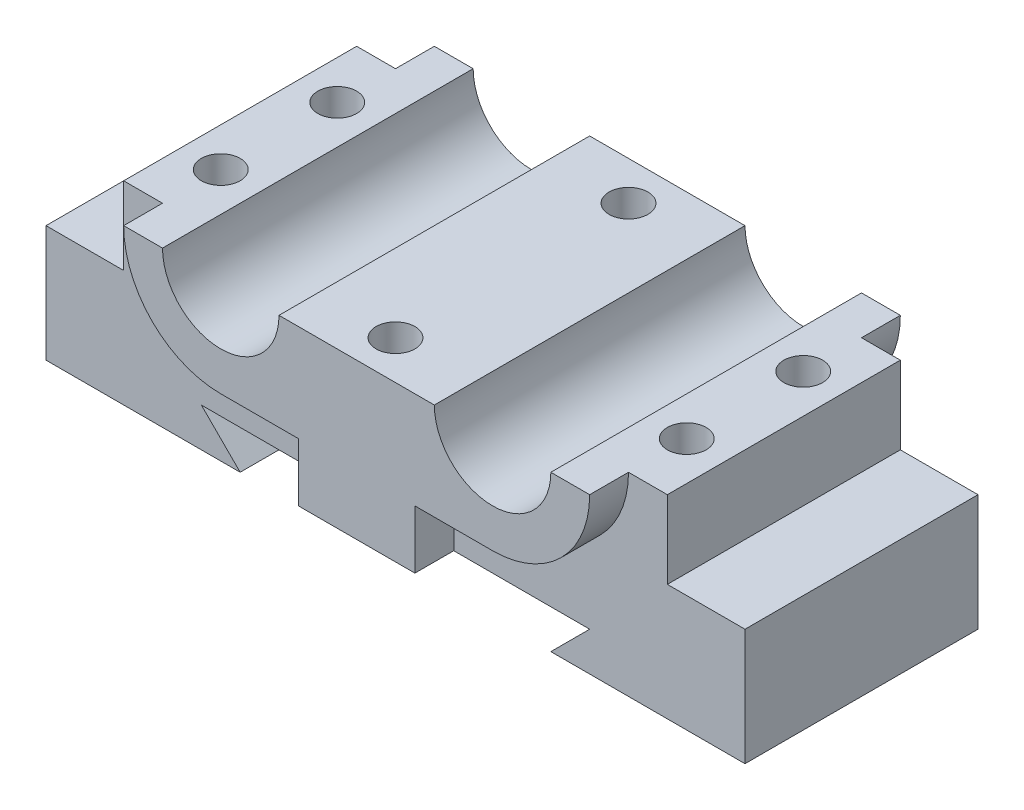
SolidWorks part; units mm, degrees
ref_plane "Front Plane" through (0, 0, 0) normal (0, 0, 1) x (1, 0, 0)
ref_plane "Top Plane" through (0, 0, 0) normal (0, 1, 0) x (1, 0, 0)
ref_plane "Right Plane" through (0, 0, 0) normal (1, 0, 0) x (0, 0, -1)
sketch "Sketch1" plane through (0, 0, 0) normal (0, 0, 1) x (1, 0, 0)
  line L0 (114.3, 0) -> (50.8, 0)
  line L1 (114.3, 0) -> (114.3, 38.1)
  line L2 (114.3, 38.1) -> (88.9, 38.1)
  line L3 (88.9, 38.1) -> (88.9, 63.5)
  line L4 (88.9, 63.5) -> (63.5, 63.5)
  line L5 (25.4, 63.5) -> (-25.4, 63.5)
  line L6 (0, 63.5) -> (0, 0) construction
  line L7 (-114.3, 0) -> (-114.3, 38.1)
  line L8 (-114.3, 38.1) -> (-88.9, 38.1)
  line L9 (-88.9, 38.1) -> (-88.9, 63.5)
  line L10 (-88.9, 63.5) -> (-63.5, 63.5)
  line L11 (19.05, 0) -> (19.05, 12.7)
  line L12 (19.05, 12.7) -> (63.5, 12.7)
  line L13 (-19.05, 0) -> (-19.05, 12.7)
  line L14 (50.8, 0) -> (63.5, 12.7)
  line L15 (-19.05, 12.7) -> (-63.5, 12.7)
  line L16 (-50.8, 0) -> (-63.5, 12.7)
  line L17 (50.8, 0) -> (50.1903, -0.6146)
  line L18 (-114.3, 0) -> (-50.8, 0)
  line L19 (-19.05, 0) -> (19.05, 0)
  line L20 (44.45, 31.75) -> (19.05, 31.75)
  line L21 (19.05, 31.75) -> (19.05, 12.7)
  line L22 (-44.45, 31.75) -> (-19.05, 31.75)
  line L23 (-19.05, 31.75) -> (-19.05, 12.7)
  arc A0 (44.45, 31.75) -> (76.2, 63.5) centre (44.45, 63.5) ccw
  arc A1 (25.4, 63.5) -> (63.5, 63.5) centre (44.45, 63.5) ccw
  arc A2 (-25.4, 63.5) -> (-63.5, 63.5) centre (-44.45, 63.5) cw
  arc A3 (-44.45, 31.75) -> (-76.2, 63.5) centre (-44.45, 63.5) cw
  dimension "D6" = 19.05
  dimension "D7" = 31.75
  dimension "D1" = 228.6
  dimension "D2" = 38.1
  dimension "D3" = 25.4
  dimension "D4" = 25.4
  dimension "D5" = 19.05
  dimension "D8" = 50.8
  dimension "D10" = 12.7
extrude "Boss-Extrude1" add sketch "Sketch1" along normal mid plane 76.2 contours A0 L20 L21 L12 L14 L0 L1 L2 L3 L4 | L22 A3 L10 L9 L8 L7 L18 L16 L15 L23 region at (74.5945, 23.4873, 0) region at (-74.5945, 23.4873, 0)
extrude "Boss-Extrude2" add sketch "Sketch1<3>" along normal mid plane 101.6 contours L5 L6 L19 L11 L21 L20 A0 L4 A1 | L6 L5 A2 L10 A3 L22 L23 L13 L19 region at (25.7616, 37.9083, 0) region at (-25.7616, 37.9083, 0)
sketch "Sketch1<3>" plane through (0, 0, 0) normal (0, 0, 1) x (1, 0, 0) same geometry as "Sketch1"
sketch "Sketch2" plane through (0, 63.5, 0) normal (0, 1, 0) x (1, 0, 0)
  line L0 (-88.9, 0) -> (88.9, 0) construction
  line L1 (-88.9, -38.1) -> (-88.9, 38.1) construction
  line L2 (88.9, -38.1) -> (88.9, 38.1) construction
  line L3 (0, 50.8) -> (0, -50.8) construction
  line L4 (25.4, 50.8) -> (-25.4, 50.8) construction
  line L5 (25.4, -50.8) -> (-25.4, -50.8) construction
  line L6 (-88.9, -38.1) -> (-88.9, 38.1) construction
  circle A0 centre (-76.2, 19.05) radius 6.35
  circle A1 centre (0, 38.1) radius 6.35
  circle A2 centre (76.2, 19.05) radius 6.35
  circle A3 centre (76.2, -19.05) radius 6.35
  circle A4 centre (0, -38.1) radius 6.35
  circle A5 centre (-76.2, -19.05) radius 6.35
  dimension "D1" = 12.7
  dimension "D2" = 19.05
  dimension "D3" = 12.7
  dimension "D4" = 38.1
extrude "Cut-Extrude2" cut sketch "Sketch2" against normal blind 28.575
sketch "Sketch3" plane through (0, 0, 0) normal (0, -1, 0) x (1, 0, 0)
  line L0 (-19.05, 50.8) -> (19.05, 50.8)
  line L1 (19.05, 50.8) -> (19.05, -50.8)
  line L2 (19.05, -50.8) -> (-19.05, -50.8)
  line L3 (-19.05, 50.8) -> (-19.05, -50.8)
extrude "Cut-Extrude3" cut sketch "Sketch3" against normal up to surface (12.7 mm away) up to face at (-41.275, 12.7, 0)
